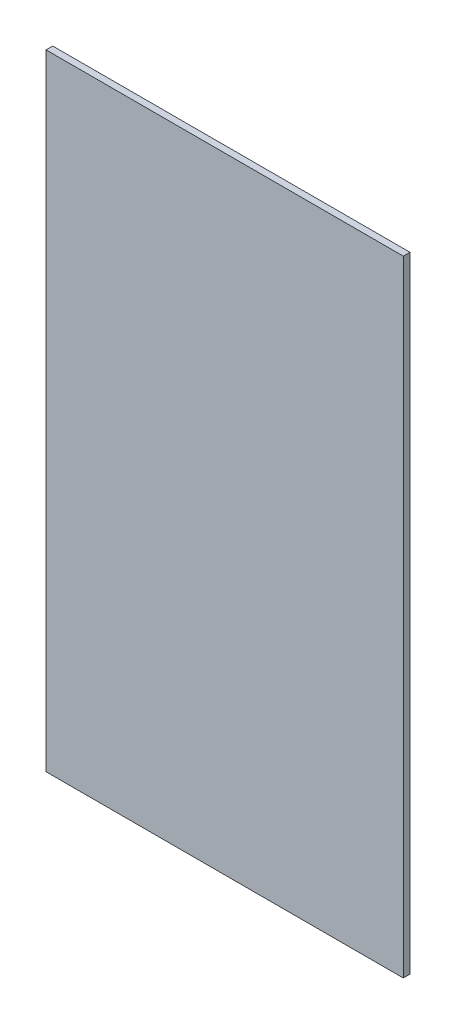
SolidWorks part; units mm, degrees
material "PC High Viscosity"
ref_plane "Front Plane" through (0, 0, 0) normal (0, 0, 1) x (1, 0, 0)
ref_plane "Top Plane" through (0, 0, 0) normal (0, 1, 0) x (1, 0, 0)
ref_plane "Right Plane" through (0, 0, 0) normal (1, 0, 0) x (0, 0, -1)
sketch "Sketch1" plane through (0, 0, 0) normal (0, 0, 1) x (1, 0, 0)
  line L1 (-80, -140) -> (80, -140)
  line L2 (-80, -140) -> (-80, 140)
  line L3 (-80, 140) -> (80, 140)
  line L4 (80, -140) -> (80, 140)
  line L5 (-80, -140) -> (80, 140) construction
  line L6 (-80, 140) -> (80, -140) construction
  point P0 (0, 0)
  dimension "D1" = 160
  dimension "D2" = 280
extrude "Boss-Extrude1" add sketch "Sketch1" along normal mid plane 3
sketch "Sketch2" [suppressed] plane through (0, 0, 1.5) normal (0, 0, 1) x (1, 0, 0)
  line L0 (106, 140) -> (104, 140) construction
  line L1 (-155.214, 211.8255) -> (203.9552, 211.8255)
  line L2 (-155.214, 211.8255) -> (-155.214, 140)
  line L3 (-155.214, 140) -> (203.9552, 140)
  line L4 (203.9552, 211.8255) -> (203.9552, 140)
extrude "Cut-Extrude1" [suppressed] cut sketch "Sketch2" against normal through all
